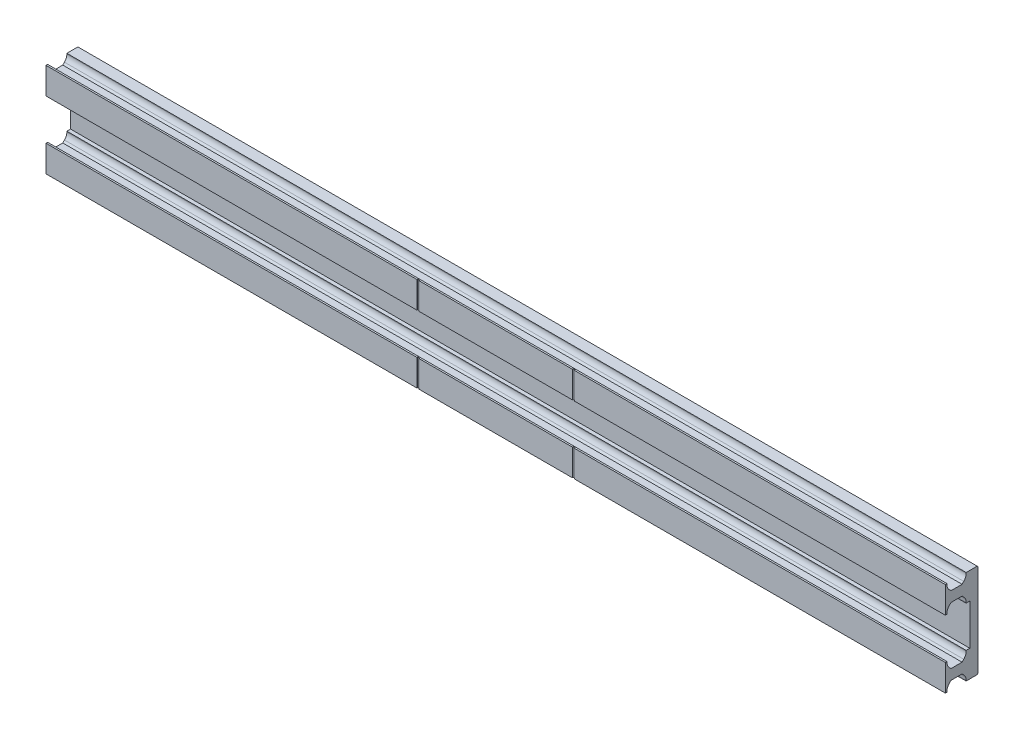
SolidWorks part; units mm, degrees
ref_plane "Front" through (0, 0, 0) normal (0, 0, 1) x (1, 0, 0)
ref_plane "Top" through (0, 0, 0) normal (0, 1, 0) x (1, 0, 0)
ref_plane "Right" through (0, 0, 0) normal (1, 0, 0) x (0, 0, -1)
sketch "Sketch1" plane through (0, 0, 0) normal (0, 0, 1) x (1, 0, 0)
  line L0 (110, -4.5) -> (110, 4.5) construction
  line L1 (-110, 11.5) -> (110, 11.5)
  line L2 (-110, 11.5) -> (-110, -11.5)
  line L3 (-110, -11.5) -> (110, -11.5)
  line L4 (110, 11.5) -> (110, -11.5)
  line L5 (-110, 11.5) -> (110, -11.5) construction
  line L6 (-110, -11.5) -> (110, 11.5) construction
  point P0 (0, 0)
  dimension "D1" = 7
extrude "Boss-Extrude1" add sketch "Sketch1" against normal blind 2
sketch "Sketch2" plane through (0, 0, 0) normal (0, 0, 1) x (1, 0, 0)
  line L0 (110, 11.5) -> (110, -11.5) construction
  line L1 (-110, 11.5) -> (110, 11.5)
  line L2 (-110, 11.5) -> (-110, 5)
  line L3 (-110, 5) -> (110, 5)
  line L4 (110, 11.5) -> (110, 5)
  line L5 (-110, -11.5) -> (-110, 11.5) construction
  line L6 (-110, -11.5) -> (110, -11.5)
  line L7 (-110, -11.5) -> (-110, -5)
  line L8 (-110, -5) -> (110, -5)
  line L9 (110, -11.5) -> (110, -5)
  line L11 (-110, 4.5) -> (110, 4.5) construction
  dimension "D1" = 0.5
extrude "Boss-Extrude2" add sketch "Sketch2" along normal offset from surface (6 mm away) 1
ref_plane "Center of Slots" through (0, 8.25, 0) normal (0, -1, 0) x (-1, 0, 0)
sketch "Sketch5" plane through (0, 0, 0) normal (1, 0, 0) x (0, 0, -1)
  line L16 (-1.9, 7) -> (-4.6, 7)
  line L17 (-1.9, 7) -> (-4.6, 7)
  line L18 (-4.6, 7) -> (-5.0142, 6.5858)
  line L19 (-4.6, 7) -> (-5.0142, 6.5858)
  line L20 (-5.6, 5.1716) -> (-5.6, 4.3284)
  line L21 (-5.6, 5.1716) -> (-5.6, 4.3284)
  line L22 (-5.0142, 2.9142) -> (-4.6, 2.5)
  line L23 (-5.0142, 2.9142) -> (-4.6, 2.5)
  line L24 (-4.6, 2.5) -> (-1.9, 2.5)
  line L25 (-4.6, 2.5) -> (-1.9, 2.5)
  line L26 (-1.9, 2.5) -> (-1.4858, 2.9142)
  line L27 (-1.9, 2.5) -> (-1.4858, 2.9142)
  line L28 (-0.9, 4.3284) -> (-0.9, 5.1716)
  line L29 (-0.9, 4.3284) -> (-0.9, 5.1716)
  line L30 (-1.4858, 6.5858) -> (-1.9, 7)
  line L31 (-1.4858, 6.5858) -> (-1.9, 7)
  arc A12 (-5.0142, 6.5858) -> (-5.6, 5.1716) centre (-3.6, 5.1716) ccw
  arc A13 (-5.0142, 6.5858) -> (-5.6, 5.1716) centre (-3.6, 5.1716) ccw
  arc A14 (-5.6, 4.3284) -> (-5.0142, 2.9142) centre (-3.6, 4.3284) ccw
  arc A15 (-5.6, 4.3284) -> (-5.0142, 2.9142) centre (-3.6, 4.3284) ccw
  arc A16 (-1.4858, 2.9142) -> (-0.9, 4.3284) centre (-2.9, 4.3284) ccw
  arc A17 (-1.4858, 2.9142) -> (-0.9, 4.3284) centre (-2.9, 4.3284) ccw
  arc A18 (-0.9, 5.1716) -> (-1.4858, 6.5858) centre (-2.9, 5.1716) ccw
  arc A19 (-0.9, 5.1716) -> (-1.4858, 6.5858) centre (-2.9, 5.1716) ccw
  dimension "D1" = 0
extrude "Middle Slot" cut sketch "Sketch5" against normal through all both and the other way through all
mirror "Middle Slots" about plane through (0, 0, 0) normal (0, 1, 0) of "Middle Slot"
sketch "Sketch7" plane through (0, 0, 0) normal (1, 0, 0) x (0, 0, -1)
  line L8 (-1.875, 13.975) -> (-4.625, 13.975)
  line L9 (-4.625, 13.975) -> (-5.0142, 13.5858)
  line L10 (-5.6, 12.1716) -> (-5.6, 11.3284)
  line L11 (-5.0142, 9.9142) -> (-4.6, 9.5)
  line L12 (-4.6, 9.5) -> (-1.9, 9.5)
  line L13 (-1.9, 9.5) -> (-1.4858, 9.9142)
  line L14 (-0.9, 11.3284) -> (-0.9, 12.1716)
  line L15 (-1.4858, 13.5858) -> (-1.875, 13.975)
  line L16 (-1.875, 13.975) -> (-4.625, 13.975)
  line L17 (-4.625, 13.975) -> (-5.0142, 13.5858)
  line L18 (-5.6, 12.1716) -> (-5.6, 11.3284)
  line L19 (-5.0142, 9.9142) -> (-4.6, 9.5)
  line L20 (-4.6, 9.5) -> (-1.9, 9.5)
  line L21 (-1.9, 9.5) -> (-1.4858, 9.9142)
  line L22 (-0.9, 11.3284) -> (-0.9, 12.1716)
  line L23 (-1.4858, 13.5858) -> (-1.875, 13.975)
  arc A4 (-5.0142, 13.5858) -> (-5.6, 12.1716) centre (-3.6, 12.1716) ccw
  arc A5 (-5.6, 11.3284) -> (-5.0142, 9.9142) centre (-3.6, 11.3284) ccw
  arc A6 (-1.4858, 9.9142) -> (-0.9, 11.3284) centre (-2.9, 11.3284) ccw
  arc A7 (-0.9, 12.1716) -> (-1.4858, 13.5858) centre (-2.9, 12.1716) ccw
  arc A8 (-5.0142, 13.5858) -> (-5.6, 12.1716) centre (-3.6, 12.1716) ccw
  arc A9 (-5.6, 11.3284) -> (-5.0142, 9.9142) centre (-3.6, 11.3284) ccw
  arc A10 (-1.4858, 9.9142) -> (-0.9, 11.3284) centre (-2.9, 11.3284) ccw
  arc A11 (-0.9, 12.1716) -> (-1.4858, 13.5858) centre (-2.9, 12.1716) ccw
  dimension "D1" = 0
extrude "Top Slot" cut sketch "Sketch7" against normal through all both and the other way through all
mirror "Top Slots" about plane through (0, 0, 0) normal (0, 1, 0) of "Top Slot"
chamfer "Deburs" distance 0.2 angle 45 2 edges at (0, -11.5, -2) (0, 11.5, -2)
sketch "Sketch8" plane through (0, 0, 6) normal (0, 0, -1) x (-1, 0, 0)
  line L0 (-19, -14.5) -> (-19, 14.5)
  line L1 (-110, 11.5) -> (-110, -11.5) construction
  line L2 (110, 11.5) -> (-110, 11.5) construction
  line L3 (110, -11.5) -> (-110, -11.5) construction
  dimension "D1" = 91
  dimension "D2" = 3
  dimension "D3" = 3
extrude "Fill Marker" cut sketch "Sketch8" along normal blind 0.2 thin thin type mid plane wall 0.5
mirror "Fill Markers" about plane through (0, 0, 0) normal (1, 0, 0) of "Fill Marker"
